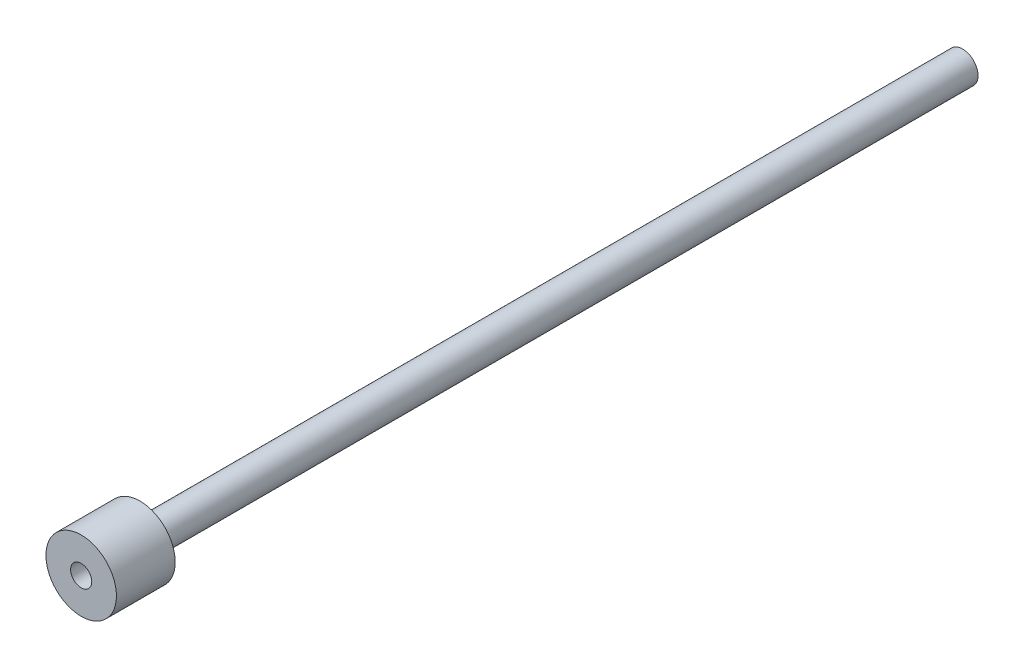
SolidWorks part; units mm, degrees
ref_plane "Front Plane" through (0, 0, 0) normal (0, 0, 1) x (1, 0, 0)
ref_plane "Top Plane" through (0, 0, 0) normal (0, 1, 0) x (1, 0, 0)
ref_plane "Right Plane" through (0, 0, 0) normal (1, 0, 0) x (0, 0, -1)
sketch "Sketch1" plane through (0, 0, 0) normal (0, 0, 1) x (1, 0, 0)
  circle A0 centre (0, 0) radius 12
  dimension "D1" = 24
extrude "Boss-Extrude1" add sketch "Sketch1" along normal blind 20
sketch "Sketch2" plane through (0, 0, 0) normal (0, 0, -1) x (-1, 0, 0)
  circle A0 centre (0, 0) radius 9.5
  circle A1 centre (0, 0) radius 5.25
  dimension "D1" = 19
  dimension "D2" = 10.5
extrude "Cut-Extrude1" cut sketch "Sketch2" against normal blind 15
sketch "Sketch3" plane through (0, 0, 20) normal (0, 0, 1) x (1, 0, 0)
  circle A0 centre (0, 0) radius 3.6
  dimension "D1" = 7.2
extrude "Cut-Extrude2" cut sketch "Sketch3" against normal through all
sketch "Sketch4" plane through (0, 0, 0) normal (0, 0, -1) x (-1, 0, 0)
  circle A0 centre (0, 0) radius 3.6 construction
  circle A1 centre (0, 0) radius 5.25
  circle A3 centre (0, 0) radius 3.6
  circle A14 centre (0, 0) radius 5.25
  dimension "D1" = 0
extrude "Boss-Extrude2" add sketch "Sketch4" along normal blind 280
